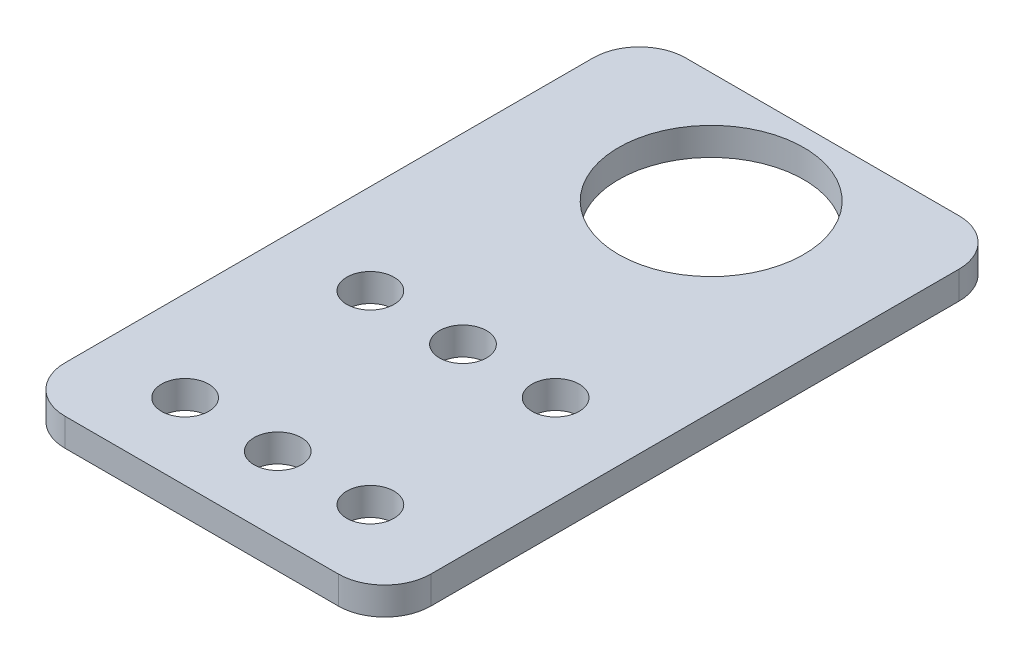
SolidWorks part; units mm, degrees
material "6061-T6 (SS)"
ref_plane "Front Plane" through (0, 0, 0) normal (0, 0, 1) x (1, 0, 0)
ref_plane "Top Plane" through (0, 0, 0) normal (0, 1, 0) x (1, 0, 0)
ref_plane "Right Plane" through (0, 0, 0) normal (1, 0, 0) x (0, 0, -1)
sketch "Sketch1" plane through (0, 0, 0) normal (0, 1, 0) x (1, 0, 0)
  line L0 (-19.75, 0) -> (0, 0) construction
  line L1 (14.75, -33.5) -> (-14.75, -33.5)
  line L2 (19.75, -28.5) -> (19.75, 28.5)
  line L3 (14.75, 33.5) -> (-14.75, 33.5)
  line L4 (-19.75, -28.5) -> (-19.75, 28.5)
  line L5 (0, 33.5) -> (0, 0) construction
  line L9 (10, -25.29) -> (0, -25.29) construction
  arc A0 (-14.75, -33.5) -> (-19.75, -28.5) centre (-14.75, -28.5) cw
  arc A1 (14.75, -33.5) -> (19.75, -28.5) centre (14.75, -28.5) ccw
  arc A2 (19.75, 28.5) -> (14.75, 33.5) centre (14.75, 28.5) ccw
  arc A3 (-14.75, 33.5) -> (-19.75, 28.5) centre (-14.75, 28.5) ccw
  circle A4 centre (0, 26.5) radius 2.55
  circle A7 centre (10, -25.29) radius 2.55
  circle A8 centre (10, -5.29) radius 2.55
  circle A9 centre (0, -25.29) radius 2.55
  circle A10 centre (0, -5.29) radius 2.55
  circle A11 centre (-10, -25.29) radius 2.55
  circle A12 centre (-10, -5.29) radius 2.55
  dimension "D2" = 5
  dimension "D3" = 7
  dimension "D7" = 20
  dimension "D10" = 3
  dimension "D8" = 9.75
  dimension "D6" = 5.1
  dimension "D1" = 67
  dimension "D9" = 39.5
  dimension "D11" = 10
  dimension "D12" = 8.21
extrude "Boss-Extrude1" add sketch "Sketch1" along normal blind 3
sketch "Sketch2" plane through (0, 3, 0) normal (0, 1, 0) x (1, 0, 0)
  line L0 (14.75, 33.5) -> (-14.75, 33.5) construction
  line L1 (-14.75, -33.5) -> (14.75, -33.5) construction
  circle A0 centre (0, 21.5) radius 19.75 construction
  circle A1 centre (0, 21.5) radius 10
  point P2 (0, 33.5)
  point P5 (0, -33.5)
  dimension "D1" = 0
  dimension "D2" = 55
extrude "Cut-Extrude2" cut sketch "Sketch2" against normal through all
